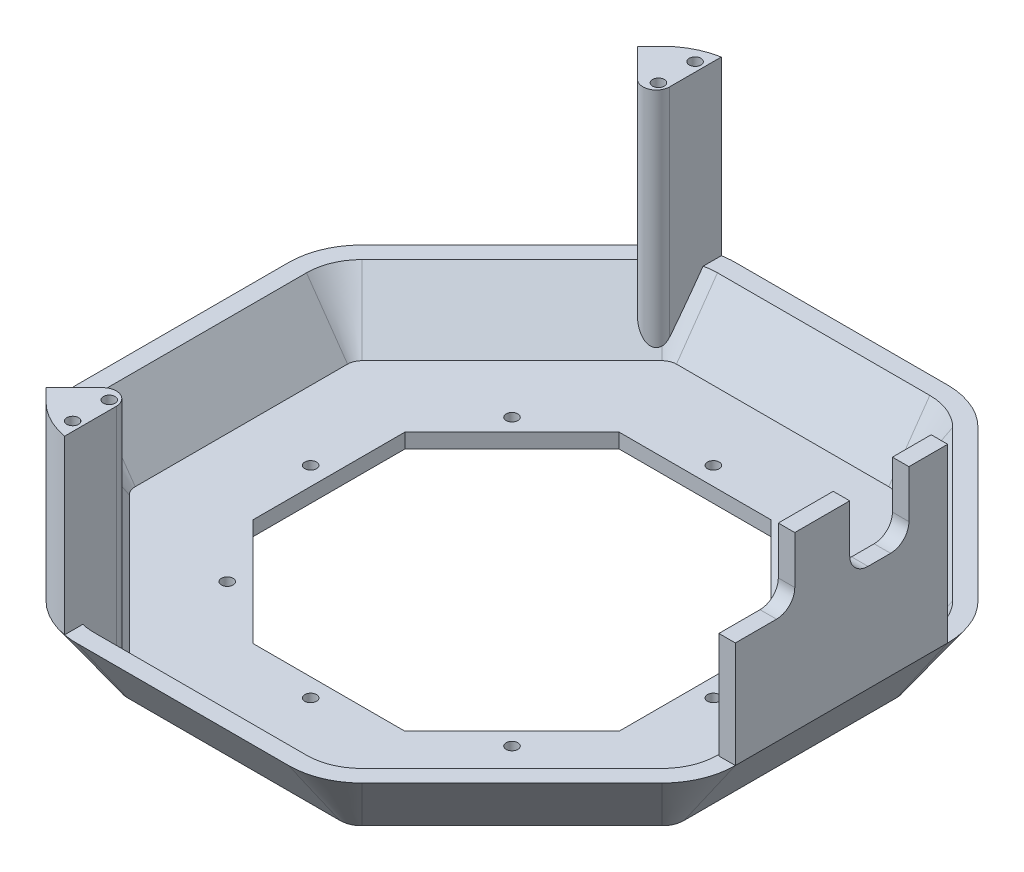
SolidWorks part; units mm, degrees
ref_plane "Front Plane" through (0, 0, 0) normal (0, 0, 1) x (1, 0, 0)
ref_plane "Top Plane" through (0, 0, 0) normal (0, 1, 0) x (1, 0, 0)
ref_plane "Right Plane" through (0, 0, 0) normal (1, 0, 0) x (0, 0, -1)
sketch "Sketch1" plane through (0, 0, 0) normal (0, 1, 0) x (1, 0, 0)
  line L1 (90, -28.9949) -> (90, 28.9949)
  line L2 (84.1421, 43.1371) -> (43.1371, 84.1421)
  line L3 (28.9949, 90) -> (-28.9949, 90)
  line L4 (-43.1371, 84.1421) -> (-84.1421, 43.1371)
  line L5 (-90, 28.9949) -> (-90, -28.9949)
  line L6 (-84.1421, -43.1371) -> (-43.1371, -84.1421)
  line L7 (-28.9949, -90) -> (28.9949, -90)
  line L8 (43.1371, -84.1421) -> (84.1421, -43.1371)
  circle A0 centre (0, 0) radius 90 construction
  arc A1 (-90, -28.9949) -> (-84.1421, -43.1371) centre (-70, -28.9949) ccw
  arc A2 (-43.1371, -84.1421) -> (-28.9949, -90) centre (-28.9949, -70) ccw
  arc A3 (28.9949, -90) -> (43.1371, -84.1421) centre (28.9949, -70) ccw
  arc A4 (90, -28.9949) -> (84.1421, -43.1371) centre (70, -28.9949) cw
  arc A5 (90, 28.9949) -> (84.1421, 43.1371) centre (70, 28.9949) ccw
  arc A6 (43.1371, 84.1421) -> (28.9949, 90) centre (28.9949, 70) ccw
  arc A7 (-28.9949, 90) -> (-43.1371, 84.1421) centre (-28.9949, 70) ccw
  arc A8 (-84.1421, 43.1371) -> (-90, 28.9949) centre (-70, 28.9949) ccw
  dimension "D1" = 180
  dimension "D2" = 20
extrude "Initial extrude" add sketch "Sketch1" along normal blind 20
chamfer "Top chamfer" distance 20 angle 35 16 edges at (0, 20, 90) (-63.6396, 20, 63.6396) (-90, 20, 0) (-63.6396, 20, -63.6396) (0, 20, -90) (63.6396, 20, -63.6396) (90, 20, 0) (63.6396, 20, 63.6396) (-88.4776, 20, -36.6486) (-36.6486, 20, -88.4776) (36.6486, 20, -88.4776) (88.4776, 20, -36.6486) (88.4776, 20, 36.6486) (36.6486, 20, 88.4776) (-36.6486, 20, 88.4776) (-88.4776, 20, 36.6486) first distance on face at (0, 10, 90) first distance on face at (-63.6396, 10, 63.6396) first distance on face at (-90, 10, 0) first distance on face at (-63.6396, 10, -63.6396) first distance on face at (0, 10, -90) first distance on face at (63.6396, 10, -63.6396) first distance on face at (90, 10, 0) first distance on face at (63.6396, 10, 63.6396) first distance on face at (-87.7743, 10, -36.3573) first distance on face at (-36.3573, 10, -87.7743) first distance on face at (36.3573, 10, -87.7743) first distance on face at (87.7743, 10, -36.3573) first distance on face at (87.7743, 10, 36.3573) first distance on face at (36.3573, 10, 87.7743) first distance on face at (-36.3573, 10, 87.7743) first distance on face at (-87.7743, 10, 36.3573)
shell "Top shell" thickness 4 removed face at (0, 0, 0)
sketch "Sketch2" plane through (0, 20, 0) normal (0, 1, 0) x (1, 0, 0)
  line L1 (20.7107, 50) -> (-20.7107, 50)
  line L2 (-20.7107, 50) -> (-50, 20.7107)
  line L3 (-50, 20.7107) -> (-50, -20.7107)
  line L4 (-50, -20.7107) -> (-20.7107, -50)
  line L5 (-20.7107, -50) -> (20.7107, -50)
  line L6 (20.7107, -50) -> (50, -20.7107)
  line L7 (50, -20.7107) -> (50, 20.7107)
  line L8 (50, 20.7107) -> (20.7107, 50)
  circle A0 centre (0, 0) radius 50 construction
  dimension "D1" = 100
extrude "Interior hex hole" cut sketch "Sketch2" against normal through all
sketch "Sketch3" plane through (0, 16, 0) normal (0, -1, 0) x (1, 0, 0)
  line L0 (-50, -20.7107) -> (-50, 20.7107) construction
  circle A0 centre (-55, 0) radius 1.6
  circle A1 centre (-38.8909, 38.8909) radius 1.6
  circle A2 centre (0, 55) radius 1.6
  circle A3 centre (38.8909, 38.8909) radius 1.6
  circle A4 centre (55, 0) radius 1.6
  circle A5 centre (38.8909, -38.8909) radius 1.6
  circle A6 centre (0, -55) radius 1.6
  circle A7 centre (-38.8909, -38.8909) radius 1.6
  point P22 (0, 0)
  dimension "D1" = 3.2
  dimension "D2" = 5
  dimension "D3" = 8
extrude "Top screw holes" cut sketch "Sketch3" against normal through all
ref_plane "Plane1" through (0, 0, 0) normal (0, 0, -1) x (-1, 0, 0)
sketch "Sketch6" plane through (0, 0, 0) normal (0, -1, 0) x (1, 0, 0)
  line L0 (-90, -28.9949) -> (-90, 28.9949) construction
  line L1 (-90, -28.9949) -> (-85.5, -28.9949)
  line L2 (-90, -28.9949) -> (-90, 28.9949)
  line L3 (-90, 28.9949) -> (-85.5, 28.9949)
  line L4 (-85.5, -28.9949) -> (-85.5, 28.9949)
  dimension "D1" = 4.5
extrude "Boss-Extrude2" add sketch "Sketch6" along normal blind 29
sketch "Sketch7" plane through (0, -29, 0) normal (0, -1, 0) x (1, 0, 0)
  line L0 (-90, 28.9949) -> (-90, -28.9949) construction
  line L1 (-90, -2.2382) -> (-85.5, -2.2382)
  line L2 (-90, -2.2382) -> (-90, 12.7618)
  line L3 (-90, 12.7618) -> (-85.5, 12.7618)
  line L4 (-85.5, -2.2382) -> (-85.5, 12.7618)
  line L6 (-85.5, -28.9949) -> (-85.5, 28.9949) construction
  line L8 (-90, -18.4069) -> (-85.5, -18.4069)
  line L9 (-90, -18.4069) -> (-90, -28.9949)
  line L10 (-90, -28.9949) -> (-85.5, -28.9949)
  line L11 (-85.5, -18.4069) -> (-85.5, -28.9949)
  line L12 (-84.1603, -16.3069) -> (-90.5103, -16.3069) construction
  line L13 (-87.5639, -4.3054) -> (-90.5103, -4.3054) construction
  line M3 (-90, 28.9949) -> (-90, -28.9949)
  line M4 (-90, -28.9949) -> (-85.5, -28.9949)
  line M5 (-85.5, -28.9949) -> (-85.5, 28.9949)
  dimension "D1" = 15
  dimension "D2" = 2.1
  dimension "D3" = 2.0672
extrude "Boss-Extrude3" add sketch "Sketch7" along normal blind 18 contours L8 M3 M4 M5 | L3 L4 L1 L2 region at (-87.75, -29, -23.7009)
ref_plane "Plane2" through (0, 0, 0) normal (0, -1, 0) x (-1, 0, 0)
fillet "Fillet1" radius 5 3 edges at (-87.75, -29, 12.7618) (-87.75, -29, -2.2382) (-87.75, -29, -18.4069)
move or copy body "Body-Move/Copy1" bodies to move or copy 109 copy no rotation origin (0, -13.5, 0) rotation axis (0, 0, 1) rotation angle 180
sketch "Sketch8" plane through (0, -27, 0) normal (0, 1, 0) x (1, 0, 0)
  line L5 (-32.5154, -89.6877) -> (-32.5154, -75.5751)
  line L11 (-43.1371, -84.1421) -> (-84.1421, -43.1371) construction
  line L12 (-43.1371, -84.1421) -> (-46.5212, -80.758)
  line L13 (-38.7542, -72.9909) -> (-46.5212, -80.758)
  arc A8 (-43.1371, -84.1421) -> (-32.5154, -89.6877) centre (-28.9949, -70) ccw
  arc A9 (-43.1371, -84.1421) -> (-28.9949, -90) centre (-28.9949, -70) ccw construction
  arc A10 (-32.5154, -75.5751) -> (-38.7542, -72.9909) centre (-36.17, -75.5751) ccw
  arc M11 (-28.9949, -85.1169) -> (-39.6842, -80.6893) centre (-28.9949, -70) cw
  line M12 (-39.6842, -80.6893) -> (-80.6893, -39.6842)
  arc M33 (-43.1371, -84.1421) -> (-28.9949, -90) centre (-28.9949, -70) ccw
extrude "Boss-Extrude5" add sketch "Sketch8" along normal up to surface and the other way up to next contours L5 M12 M33 M11 | L5 M12 M11 | A8 L5 A10 L13 L12 region at (-39.1163, -27, 83.8986) region at (-36.5475, -27, 77.8418) up to face at (87.75, 20, 5.2618)
sketch "Sketch9" plane through (0, 20, 0) normal (0, 1, 0) x (1, 0, 0)
  circle A0 centre (-35, -75) radius 1.6
  circle A1 centre (-35, -85) radius 1.6
extrude "Cut-Extrude1" cut sketch "Sketch9" against normal blind 10
mirror "Mirror2" about plane through (0, 0, 0) normal (0, 0, -1) of "Cut-Extrude1", "Boss-Extrude5"
